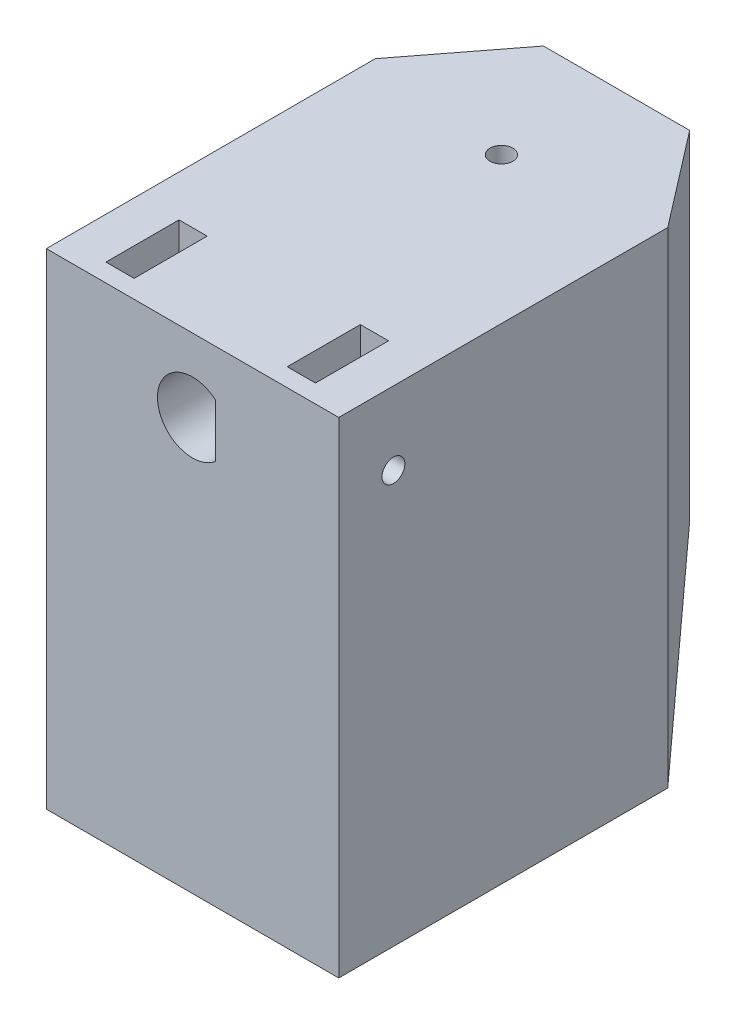
SolidWorks part; units mm, degrees
ref_plane "Front Plane" through (0, 0, 0) normal (0, 0, 1) x (1, 0, 0)
ref_plane "Top Plane" through (0, 0, 0) normal (0, 1, 0) x (1, 0, 0)
ref_plane "Right Plane" through (0, 0, 0) normal (1, 0, 0) x (0, 0, -1)
sketch "Sketch2" plane through (0, 0, 0) normal (0, 0, 1) x (1, 0, 0)
  line L0 (12.7, -6.35) -> (14.2875, -6.35)
  line L1 (-14.2875, 6.35) -> (14.2875, 6.35)
  line L2 (-14.2875, 6.35) -> (-14.2875, -6.35)
  line L3 (-14.2875, -6.35) -> (-12.7, -6.35)
  line L4 (14.2875, 6.35) -> (14.2875, -6.35)
  line L6 (-12.7, -6.35) -> (-12.7, -35.814)
  line L7 (-12.7, -35.814) -> (12.7, -35.814)
  line L8 (12.7, -6.35) -> (12.7, -35.814)
  point P5 (0, 6.35)
  point P7 (14.2875, 0)
  point P13 (0, -35.814)
  dimension "D1" = 28.575
  dimension "D2" = 12.7
  dimension "D3" = 42.164
  dimension "D4" = 25.4
extrude "Boss-Extrude1" add sketch "Sketch2" along normal blind 25.4 contours L4 L1 L2 L3 | L8 L3 L6 L7 region at (0, -14.1975, 0)
sketch "Sketch3" plane through (0, 0, 25.4) normal (0, 0, 1) x (1, 0, 0)
  line L0 (2.0031, 2.3) -> (2.0031, -2.3)
  arc A0 (2.0031, 2.3) -> (2.0031, -2.3) centre (0, 0) ccw
  dimension "D1" = 6.1
  dimension "D2" = 4.6
extrude "Cut-Extrude1" cut sketch "Sketch3" against normal blind 9.5
sketch "Sketch5" plane through (0, 0, 0) normal (0, 0, -1) x (-1, 0, 0)
  line L0 (14.2875, 6.35) -> (-14.2875, 6.35) construction
  line L1 (-12.7, 6.35) -> (12.7, 6.35)
  line L2 (-12.7, 6.35) -> (-12.7, -35.814)
  line L3 (-12.7, -35.814) -> (12.7, -35.814)
  line L4 (12.7, 6.35) -> (12.7, -35.814)
  line L5 (12.7, -6.35) -> (12.7, -35.814) construction
  line L6 (-12.7, -6.35) -> (-12.7, -35.814) construction
  dimension "D1" = 42.164
extrude "Boss-Extrude2" add sketch "Sketch5" along normal blind 11.43
sketch "Sketch6" plane through (12.7, 0, 0) normal (1, 0, 0) x (0, 0, -1)
  line L0 (3.175, -35.814) -> (11.43, -23.0188)
  line L1 (-25.4, -35.814) -> (11.43, -35.814) construction
  line L2 (11.43, 6.35) -> (11.43, -35.814) construction
  line L3 (11.43, -23.0188) -> (11.43, -35.814)
  line L4 (11.43, -35.814) -> (3.175, -35.814)
  dimension "D1" = 3.175
  dimension "D2" = 23.0188
extrude "Cut-Extrude2" cut sketch "Sketch6" against normal up to next
sketch "Sketch7" plane through (0, -35.814, 0) normal (0, -1, 0) x (1, 0, 0)
  line L0 (-12.7, -11.43) -> (-12.7, -3.175)
  line L1 (-12.7, -3.175) -> (-6.35, -11.43)
  line L2 (-12.7, -11.43) -> (12.7, -11.43) construction
  line L3 (-6.35, -11.43) -> (-12.7, -11.43)
  line L4 (6.35, -11.43) -> (12.7, -3.175)
  line L5 (12.7, -3.175) -> (12.7, -11.43)
  line L6 (12.7, -11.43) -> (6.35, -11.43)
  line L7 (-6.35, -11.43) -> (6.35, -11.43) construction
  point P10 (0, -11.43)
  dimension "D1" = 12.7
extrude "Cut-Extrude3" cut sketch "Sketch7" against normal up to next
sketch "Sketch8" plane through (0, 0, -11.43) normal (0, 0, -1) x (-1, 0, 0)
  line L0 (-1.651, 2.8596) -> (1.651, 2.8596)
  arc A0 (-1.651, 2.8596) -> (1.651, 2.8596) centre (0, 0) ccw
  dimension "D1" = 6.604
  dimension "D2" = 3.302
extrude "Cut-Extrude4" cut sketch "Sketch8" against normal blind 20
sketch "Sketch10" plane through (0, -35.814, 0) normal (0, -1, 0) x (1, 0, 0)
  line L0 (-12.7, 25.4) -> (12.7, 25.4) construction
  line L1 (-9.525, 22.225) -> (9.525, 22.225)
  line L2 (-9.525, 22.225) -> (-9.525, 3.175)
  line L3 (-9.525, 3.175) -> (9.525, 3.175)
  line L4 (9.525, 22.225) -> (9.525, 3.175)
  line L5 (12.7, 25.4) -> (12.7, -3.175) construction
  line L6 (12.7, 0) -> (14.2875, 0) construction
  point P6 (0, 22.225)
  dimension "D1" = 3.175
  dimension "D2" = 3.175
  dimension "D3" = 3.175
extrude "Cut-Extrude5" cut sketch "Sketch10" against normal offset from surface (26.289 mm away) 3.175 up to face at (13.4938, -6.35, 12.7)
sketch "Sketch11" plane through (0, 0, 25.4) normal (0, 0, 1) x (1, 0, 0)
  line L1 (-14.2875, 6.35) -> (-12.7, 6.35)
  line L2 (-14.2875, 6.35) -> (-14.2875, -6.35)
  line L3 (-14.2875, -6.35) -> (-12.7, -6.35)
  line L4 (-12.7, 6.35) -> (-12.7, -6.35)
  line L5 (12.7, -6.35) -> (14.2875, -6.35)
  line L6 (12.7, -6.35) -> (12.7, 6.35)
  line L7 (12.7, 6.35) -> (14.2875, 6.35)
  line L8 (14.2875, -6.35) -> (14.2875, 6.35)
extrude "Cut-Extrude6" cut sketch "Sketch11" against normal up to next
sketch "Sketch12" plane through (12.7, 0, 0) normal (1, 0, 0) x (0, 0, -1)
  line L1 (-25.4, 0) -> (0, 0) construction
  line L2 (-25.4, -2.3) -> (-25.4, 2.3) construction
  line L3 (-15.9, 0) -> (-25.4, 0) construction
  circle A0 centre (-20.65, 0) radius 0.9922
  point P6 (-25.4, 0)
  dimension "D1" = 1.9844
extrude "Cut-Extrude7" cut sketch "Sketch12" against normal through all
sketch "Sketch13" plane through (0, 6.35, 0) normal (0, 1, 0) x (1, 0, 0)
  line L1 (0, -8.57) -> (0, 11.43) construction
  circle A0 centre (0, 1.43) radius 0.9922
  dimension "D1" = 1.9844
extrude "Cut-Extrude8" cut sketch "Sketch13" against normal up to next
ref_plane "Plane1" through (-7.875, 0, 0) normal (-1, 0, 0) x (0, 0, 1)
ref_plane "Plane2" through (7.875, 0, 0) normal (1, 0, 0) x (0, 0, -1)
sketch "Sketch14" plane through (0, 0, 0) normal (1, 0, 0) x (0, 0, -1)
  line L1 (-17.475, 1.8331) -> (-20.65, 3.6662)
  line L2 (-20.65, 3.6662) -> (-23.825, 1.8331)
  line L3 (-23.825, 1.8331) -> (-23.825, -1.8331)
  line L4 (-23.825, -1.8331) -> (-20.65, -3.6662)
  line L5 (-20.65, -3.6662) -> (-17.475, -1.8331)
  line L6 (-17.475, -1.8331) -> (-17.475, 1.8331)
  circle A0 centre (-20.65, 0) radius 3.175 construction
  point P1 (0, 0)
  dimension "D1" = 6.35
extrude "Cut-Extrude9" cut sketch "Sketch14" against normal mid plane 2.45 from surface starting at plane "Plane1"
extrude "Cut-Extrude10" cut sketch "Sketch14<2>" against normal mid plane 2.45 from surface starting at plane "Plane2"
sketch "Sketch14<2>" plane through (0, 0, 0) normal (1, 0, 0) x (0, 0, -1) same geometry as "Sketch14"
sketch "Sketch15" plane through (0, 6.35, 0) normal (0, 1, 0) x (1, 0, 0)
  line L1 (-9.1, -17.475) -> (-6.65, -17.475)
  line L2 (-9.1, -17.475) -> (-9.1, -23.825)
  line L3 (-9.1, -23.825) -> (-6.65, -23.825)
  line L4 (-6.65, -17.475) -> (-6.65, -23.825)
  line L5 (6.65, -17.475) -> (9.1, -17.475)
  line L6 (6.65, -17.475) -> (6.65, -23.825)
  line L7 (6.65, -23.825) -> (9.1, -23.825)
  line L8 (9.1, -17.475) -> (9.1, -23.825)
  point P8 (4.0333, -23.4125)
  point P9 (8.0667, -23.2445)
  point P10 (-5.2671, -21.9248)
  point P11 (-5.125, -23.825)
  point P12 (-7.575, -17.475)
  point P15 (5.125, -17.475)
  point P17 (7.575, -23.825)
extrude "Cut-Extrude11" cut sketch "Sketch15" against normal up to next
